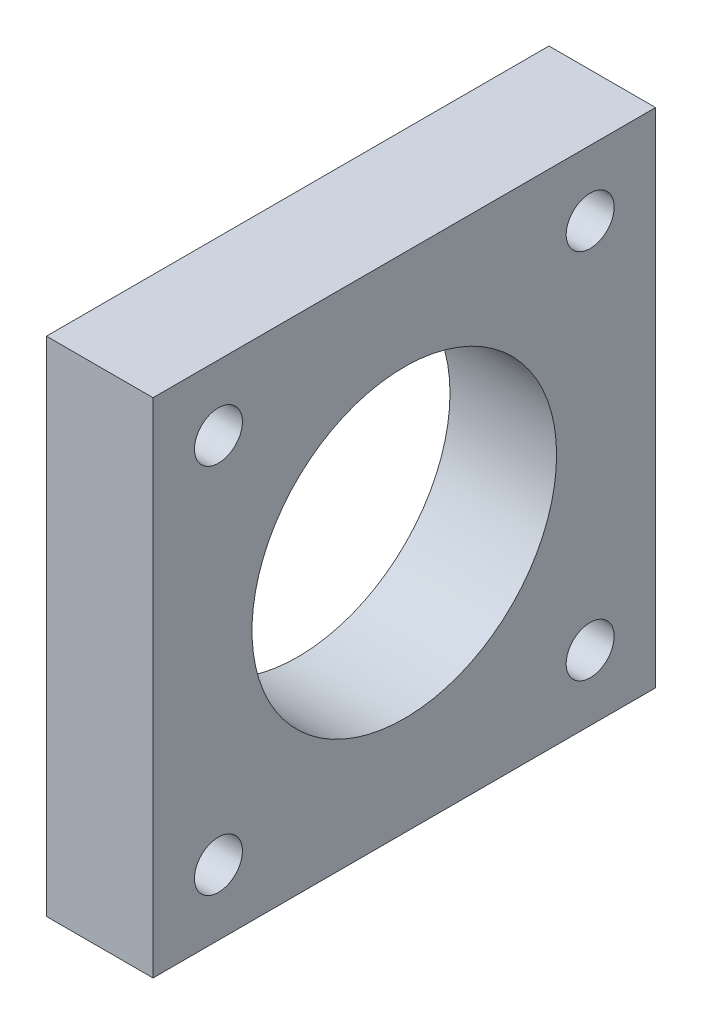
SolidWorks part; units mm, degrees
ref_plane "Front Plane" through (0, 0, 0) normal (0, 0, 1) x (1, 0, 0)
ref_plane "Top Plane" through (0, 0, 0) normal (0, 1, 0) x (1, 0, 0)
ref_plane "Right Plane" through (0, 0, 0) normal (1, 0, 0) x (0, 0, -1)
sketch "Sketch37" plane through (0, 0, 0) normal (1, 0, 0) x (0, 0, -1)
  line L1 (-15.5, 15.5) -> (15.5, 15.5) construction
  line L2 (-15.5, 15.5) -> (-15.5, -15.5) construction
  line L3 (-15.5, -15.5) -> (15.5, -15.5) construction
  line L4 (15.5, 15.5) -> (15.5, -15.5) construction
  line L5 (20.955, 20.955) -> (-20.955, 20.955)
  line L6 (20.955, 20.955) -> (20.955, -20.955)
  line L7 (20.955, -20.955) -> (-20.955, -20.955)
  line L8 (-20.955, 20.955) -> (-20.955, -20.955)
  line L9 (20.955, 20.955) -> (-20.955, -20.955) construction
  line L10 (20.955, -20.955) -> (-20.955, 20.955) construction
  line L11 (-15.5, 15.5) -> (15.5, -15.5) construction
  line L12 (-15.5, -15.5) -> (15.5, 15.5) construction
  circle A3 centre (0, 0) radius 12.7
  circle A4 centre (15.5, 15.5) radius 3
  circle A5 centre (-15.5, 15.5) radius 3
  circle A6 centre (-15.5, -15.5) radius 3
  circle A7 centre (15.5, -15.5) radius 3
  circle A8 centre (15.5, -15.5) radius 2
  circle A9 centre (-15.5, -15.5) radius 2
  circle A10 centre (-15.5, 15.5) radius 2
  circle A11 centre (15.5, 15.5) radius 2
  point P0 (0, 0)
  point P5 (0, 0)
  dimension "D5" = 25.4
  dimension "D6" = 6
  dimension "D7" = 4
  dimension "D1" = 31
  dimension "D2" = 41.91
  dimension "D3" = 41.91
  dimension "D4" = 31
extrude "Boss-Extrude27" add sketch "Sketch37" along normal blind 8.89 contours L5 L8 L7 L6 A7 A6 A5 A4 A3 | A4 A11 | A5 A10 | A6 A9 | A7 A8 region at (0, 0, -20.3623) region at (0, 15.5, -12.5849) region at (0, 15.5, 18.4151) region at (0, -15.5, 18.4151) region at (0, -15.5, -12.5849)
extrude "Cut-Extrude1" cut sketch "Sketch37<9>" along normal blind 4 contours A4 | A5 | A6 | A7
sketch "Sketch37<9>" plane through (0, 0, 0) normal (1, 0, 0) x (0, 0, -1) same geometry as "Sketch37"
